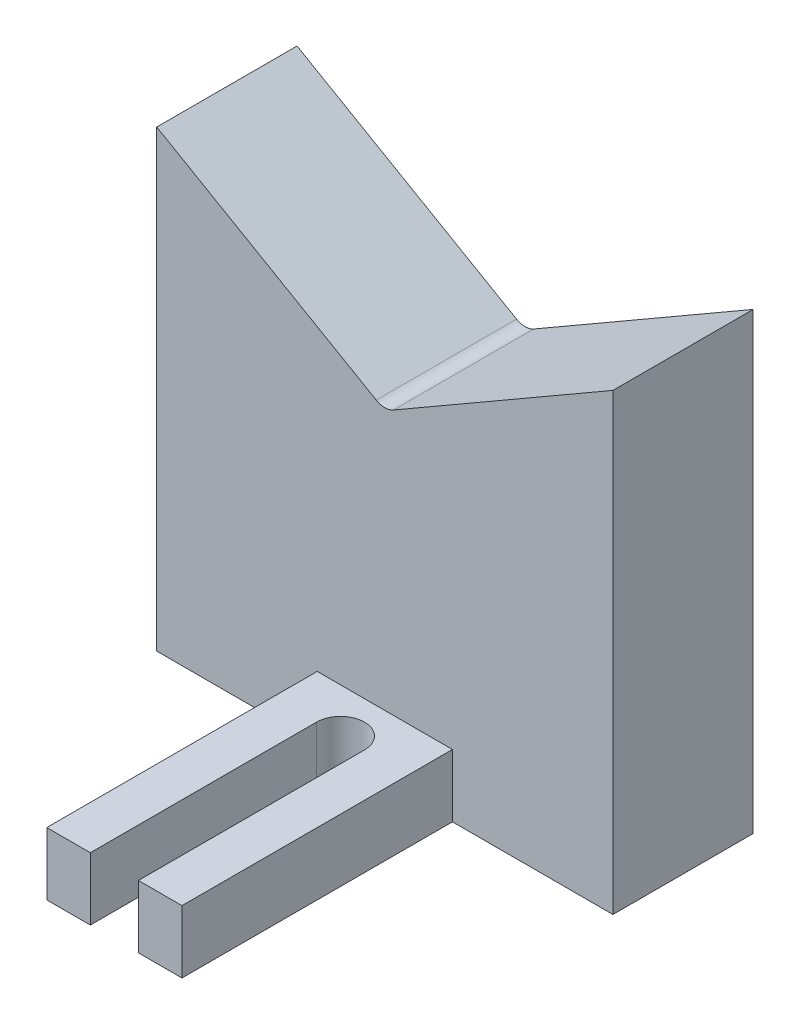
SolidWorks part; units mm, degrees
ref_plane "Front Plane" through (0, 0, 0) normal (0, 0, 1) x (1, 0, 0)
ref_plane "Top Plane" through (0, 0, 0) normal (0, 1, 0) x (1, 0, 0)
ref_plane "Right Plane" through (0, 0, 0) normal (1, 0, 0) x (0, 0, -1)
sketch "Sketch1" plane through (0, 0, 0) normal (0, 0, 1) x (1, 0, 0)
  line L0 (-33.735, 19.4769) -> (0, 0)
  line L4 (-33.735, -47.6525) -> (-33.735, 19.4769)
  line L5 (0, 0) -> (0, -47.6525) construction
  line L6 (0, 0) -> (0, 44.7273) construction
  line L14 (-38.735, 44.7273) -> (-38.735, -35.7145) construction
  line L15 (33.735, 19.4769) -> (0, 0)
  line L16 (33.735, -47.6525) -> (33.735, 19.4769)
  line L18 (-33.735, -47.6525) -> (33.735, -47.6525)
  circle A0 centre (0, 44.7273) radius 38.735 construction
  dimension "D1" = 77.47
  dimension "D4" = 10
  dimension "D2" = 92.3798
  dimension "D6" = 120
extrude "Boss-Extrude1" add sketch "Sketch1" along normal blind 20.7518
sketch "Sketch6" plane through (0, 0, 0) normal (1, 0, 0) x (0, 0, -1)
  line L0 (-10.3759, 19.4769) -> (-10.3759, -47.6525) construction
  line L1 (-20.7518, 19.4769) -> (0, 19.4769) construction
  line L2 (-20.7518, -47.6525) -> (0, -47.6525) construction
  line L4 (-60.7518, -38.3825) -> (-20.7518, -38.3825)
  line L5 (-60.7518, -38.3825) -> (-60.7518, -47.6525)
  line L6 (-60.7518, -47.6525) -> (-20.7518, -47.6525)
  line L7 (-20.7518, -38.3825) -> (-20.7518, -47.6525)
  dimension "D1" = 40
  dimension "D2" = 9.27
extrude "Boss-Extrude3" add sketch "Sketch6" along normal blind 10 and the other way blind 10
fillet "Fillet1" radius 2.54 1 edges at (0, 0, 10.3759)
sketch "Sketch7" plane through (0, 0, 0) normal (0, 1, 0) x (1, 0, 0)
  line L0 (-33.735, -10.3759) -> (33.735, -10.3759) construction
  line L3 (0, -20.7518) -> (0, -27.3068) construction
  line L4 (-33.735, -20.7518) -> (-33.735, 0) construction
  line L5 (33.735, -20.7518) -> (33.735, 0) construction
  line L6 (33.735, -20.7518) -> (1.27, -20.7518) construction
  line L7 (-10, -60.7518) -> (10, -60.7518) construction
  line L8 (-10, -20.7518) -> (10, -20.7518) construction
  line L15 (3.555, -60.7518) -> (-3.555, -60.7518)
  line L16 (0, -27.3068) -> (0, -94.1968) construction
  line L17 (-3.555, -27.3068) -> (-3.555, -94.1968)
  line L18 (3.555, -27.3068) -> (3.555, -94.1968)
  arc A6 (-3.555, -27.3068) -> (3.555, -27.3068) centre (0, -27.3068) cw
  arc A7 (3.555, -94.1968) -> (-3.555, -94.1968) centre (0, -94.1968) cw
  point P9 (0, -23.7518)
  point P13 (0, 0)
  point P14 (0, 0)
  point P21 (0, -60.7518)
  dimension "D1" = 3
  dimension "D2" = 7.11
extrude "Cut-Extrude11" cut sketch "Sketch7" against normal blind 10 from surface contours A6 L17 L15 L18 region at (0, 0, 42.6246) starting at face at (0, -38.3825, 40.7518)
